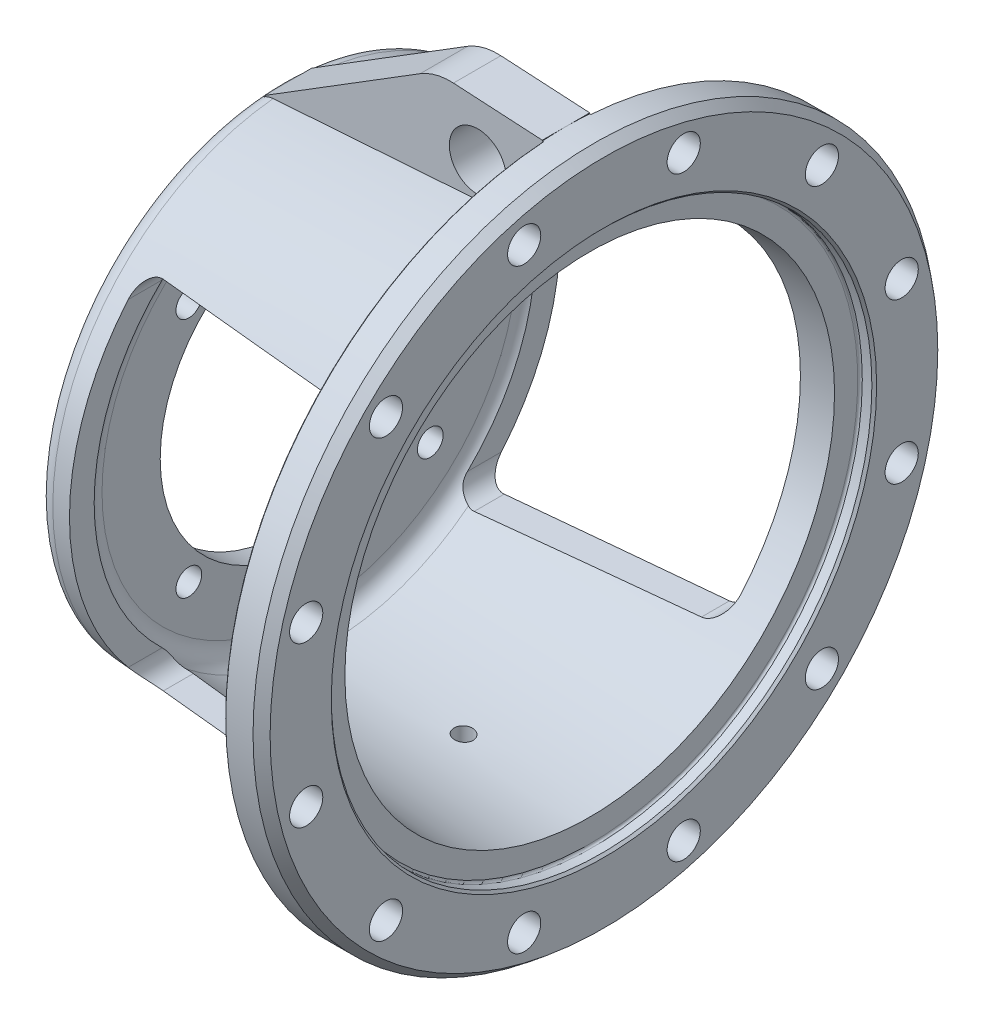
SolidWorks part; units mm, degrees
material "CD4Mc-U Duplex Stainless Steel"
ref_plane "Front Plane" through (0, 0, 0) normal (0, 0, 1) x (1, 0, 0)
ref_plane "Top Plane" through (0, 0, 0) normal (0, 1, 0) x (1, 0, 0)
ref_plane "Right Plane" through (0, 0, 0) normal (1, 0, 0) x (0, 0, -1)
sketch "Sketch2" plane through (0, 0, 0) normal (0, 0, 1) x (1, 0, 0)
  line L0 (0, 0) -> (151.2672, 0) construction
  line L1 (0, 0) -> (0, 150.7291)
  line L2 (11.8141, 163.3982) -> (180.2099, 175.1736)
  line L3 (192.024, 187.8426) -> (192.024, 228.6)
  line L4 (192.024, 228.6) -> (217.424, 228.6)
  line L5 (217.424, 228.6) -> (217.424, 180.975)
  line L6 (207.899, 163.9269) -> (32.1595, 151.638)
  line L7 (20.3454, 138.9689) -> (20.3454, 0)
  line L8 (0, 0) -> (20.3454, 0)
  line L9 (11.8141, 163.3982) -> (206.3963, 163.3982) construction
  line L10 (217.424, 180.975) -> (207.899, 180.975)
  line L11 (207.899, 180.975) -> (207.899, 163.9269)
  arc A0 (0, 150.7291) -> (11.8141, 163.3982) centre (12.7, 150.7291) cw
  arc A1 (180.2099, 175.1736) -> (192.024, 187.8426) centre (179.324, 187.8426) ccw
  arc A2 (32.1595, 151.638) -> (20.3454, 138.9689) centre (33.0454, 138.9689) ccw
  dimension "D1" = 12.7
  dimension "D2" = 163.3982
  dimension "D3" = 151.638
  dimension "D4" = 20.3454
  dimension "D5" = 4
  dimension "D6" = 25.4
  dimension "D7" = 228.6
  dimension "D8" = 217.424
  dimension "D9" = 180.975
  dimension "D10" = 9.525
revolve "Revolve1" add sketch "Sketch2" angle 360 about L0
sketch "Sketch3" plane through (0, 0, 0) normal (-1, 0, 0) x (0, 0, 1)
  circle A0 centre (0, 0) radius 133.35
  dimension "D1" = 266.7
extrude "Cut-Extrude1" cut sketch "Sketch3" against normal blind 4.7752
sketch "Sketch4" plane through (4.7752, 0, 0) normal (-1, 0, 0) x (0, 0, 1)
  circle A0 centre (0, 0) radius 100.0125
  dimension "D1" = 200.025
extrude "Cut-Extrude2" cut sketch "Sketch4" against normal up to next
sketch "Sketch5" plane through (217.424, 0, 0) normal (1, 0, 0) x (0, 0, -1)
  circle A0 centre (0, 0) radius 180.9763
  dimension "D1" = 361.9525
extrude "Cut-Extrude3" cut sketch "Sketch5" against normal blind 9.525
sketch "Sketch6" plane through (4.7752, 0, 0) normal (-1, 0, 0) x (0, 0, 1)
  line L0 (0, 0) -> (114.3, 0) construction
  line L1 (0, 0) -> (80.8223, 80.8223) construction
  circle A0 centre (0, 0) radius 114.3 construction
  circle A1 centre (80.8223, 80.8223) radius 8.636
  point P3 (80.8223, 80.8223)
  dimension "D1" = 228.6
  dimension "D3" = 17.272
  dimension "D2" = 45
extrude "Cut-Extrude4" cut sketch "Sketch6" against normal up to next
pattern_circular "CirPattern1" count 4 over 360 about axis through (4.7752, 0, 0) along (-1, 0, 0) of "Cut-Extrude4"
sketch "Sketch7" plane through (217.424, 0, 0) normal (1, 0, 0) x (0, 0, -1)
  line L0 (0, 0) -> (206.375, 0) construction
  line L1 (0, 0) -> (199.3429, 53.4138) construction
  circle A0 centre (0, 0) radius 206.375 construction
  circle A1 centre (199.3429, 53.4138) radius 11.1125
  dimension "D1" = 412.75
  dimension "D3" = 22.225
  dimension "D2" = 15
extrude "Cut-Extrude5" cut sketch "Sketch7" against normal up to next
pattern_circular "CirPattern2" count 12 over 360 about axis through (217.424, 0, 0) along (-1, 0, 0) of "Cut-Extrude5"
sketch "Sketch8" plane through (0, 0, 0) normal (0, 0, 1) x (1, 0, 0)
  line L0 (192.024, 228.6) -> (192.024, -228.6) construction
  line L1 (192.024, 228.6) -> (192.024, 173.461)
  line L2 (5.9873, 161.5101) -> (110.2718, 226.302)
  line L3 (192.024, 228.6) -> (132.5388, 231.9782)
  line L4 (192.024, 173.461) -> (5.4488, 158.5456)
  line L5 (5.4488, 158.5456) -> (5.9873, 161.5101)
  line L6 (192.024, 228.6) -> (192.024, 173.461)
  arc A0 (11.8141, 163.3982) -> (0, 150.7291) centre (12.7, 150.7291) ccw construction
  arc A1 (132.5388, 231.9782) -> (110.2718, 226.302) centre (130.3786, 193.9395) ccw
  dimension "D1" = 76.2
  dimension "D2" = 231.9782
extrude "Boss-Extrude1" add sketch "Sketch8" along normal mid plane 31.75 contours L3 A1 L2 L5 L4 L1 region at (119.8434, 193.7127, 0)
sketch "Sketch9" plane through (0, 0, 15.875) normal (0, 0, 1) x (1, 0, 0)
  line L0 (217.424, -228.6) -> (217.424, 228.6) construction
  circle A0 centre (148.844, 194.564) radius 19.05
  dimension "D1" = 38.1
  dimension "D2" = 68.58
  dimension "D3" = 194.564
extrude "Cut-Extrude6" cut sketch "Sketch9" against normal up to next
sketch "Sketch10" plane through (0, 0, 0) normal (0, 1, 0) x (1, 0, 0)
  line L0 (217.424, -228.6) -> (217.424, 228.6) construction
  circle A0 centre (123.444, 0) radius 6.35
  dimension "D2" = 12.7
  dimension "D1" = 93.98
extrude "Cut-Extrude7" cut sketch "Sketch10" against normal up to next
sketch "Sketch11" plane through (0, 0, 0) normal (0, 0, 1) x (1, 0, 0)
  line L0 (0, 150.7291) -> (0, -150.7291) construction
  line L1 (36.5252, -119.3419) -> (173.8376, -119.3419)
  line L2 (23.8252, -106.6419) -> (23.8252, 106.6419)
  line L3 (36.5252, 119.3419) -> (173.8376, 119.3419)
  line L4 (186.5376, -106.6419) -> (186.5376, 106.6419)
  line L5 (23.8252, -119.3419) -> (186.5376, 119.3419) construction
  line L6 (23.8252, 119.3419) -> (186.5376, -119.3419) construction
  arc A0 (36.5252, -119.3419) -> (23.8252, -106.6419) centre (36.5252, -106.6419) cw
  arc A1 (173.8376, -119.3419) -> (186.5376, -106.6419) centre (173.8376, -106.6419) ccw
  arc A2 (173.8376, 119.3419) -> (186.5376, 106.6419) centre (173.8376, 106.6419) cw
  arc A3 (23.8252, 106.6419) -> (36.5252, 119.3419) centre (36.5252, 106.6419) cw
  point P0 (105.1814, 0)
  dimension "D4" = 12.7
  dimension "D1" = 162.7124
  dimension "D2" = 238.6838
  dimension "D3" = 23.8252
extrude "Cut-Extrude8" cut sketch "Sketch11" against normal through all both and the other way through all
chamfer "Chamfer1" distance 1.5875 angle 45 1 edges at (217.424, 0, -180.9763)
chamfer "Chamfer2" distance 0.7937 angle 45 1 edges at (192.024, -228.6, 0)
ref_axis "Axis1" through (148.844, 194.564, -15.875) along (0, 0, 1)
ref_axis "Axis2" through (123.444, -172.0095, 0) along (0, 1, 0)
sketch "Sketch12" plane through (217.424, 0, 0) normal (1, 0, 0) x (0, 0, -1)
  circle A0 centre (0, 0) radius 180.975
fillet "Fillet1" radius 1.524 1 edges at (207.899, 0, -180.9763)
chamfer "Chamfer3" distance 5.08 distance2 6.35 1 edges at (217.424, 0, 228.6) first distance on face at (217.424, 0, 182.5638)
